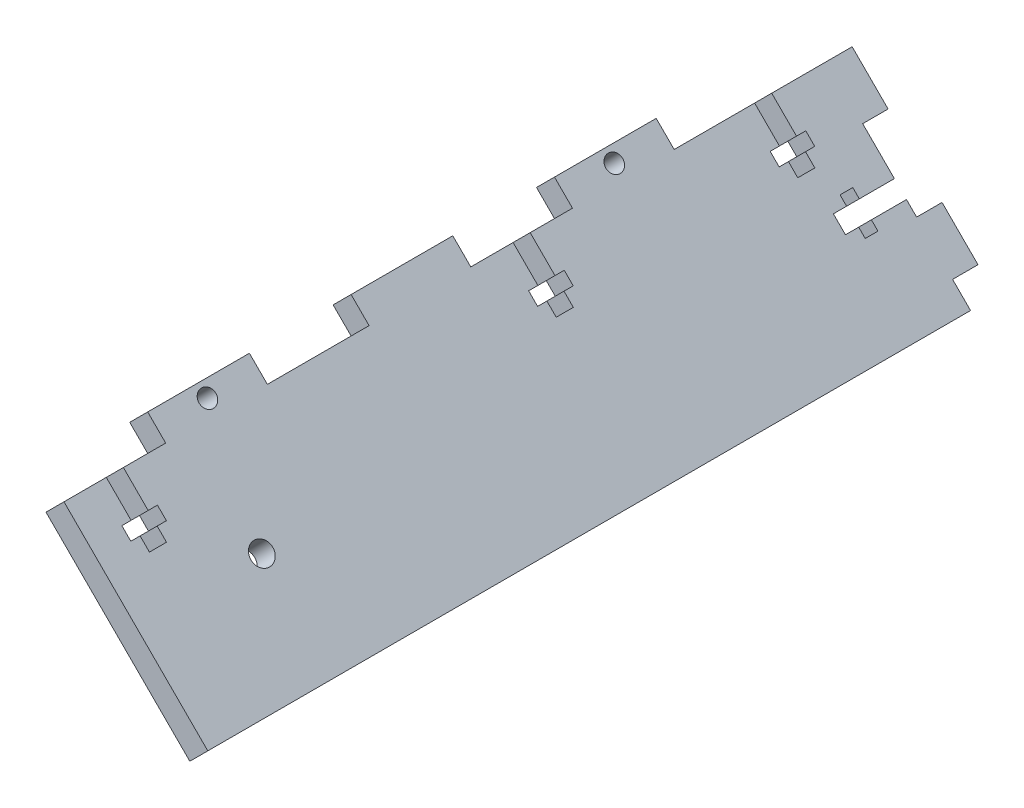
SolidWorks part; units mm, degrees
ref_plane "Front Plane" through (0, 0, 0) normal (0, 0, 1) x (1, 0, 0)
ref_plane "Top Plane" through (0, 0, 0) normal (0, 1, 0) x (1, 0, 0)
ref_plane "Right Plane" through (0, 0, 0) normal (1, 0, 0) x (0, 0, -1)
sketch "Sketch1" plane through (0, 0, 0) normal (0, 0, 1) x (1, 0, 0)
  line L0 (-105.5101, 43.1479) -> (-54.0999, -8.2622) construction
  line L1 (-20.9093, -45.9429) -> (-64.0138, -2.8384) construction
  line L2 (-59.5237, 1.6517) -> (-16.4192, -41.4528) construction
  line L3 (-73.6381, 43.6049) -> (-37.7171, 7.6839)
  line L4 (-73.6381, 43.6049) -> (-69.148, 48.095)
  line L5 (-37.7171, 7.6839) -> (-33.2269, 12.174)
  line L6 (-69.148, 48.095) -> (-33.2269, 12.174)
  line L7 (-70.046, -24.645) -> (-105.967, 11.276) construction
  line L8 (-74.5361, -29.1352) -> (-70.046, -24.645) construction
extrude "Boss-Extrude1" add sketch "Sketch1" along normal up to surface (190.5 mm away)
sketch "Sketch2" plane through (-58.6215, 58.6215, 0) normal (-0.7071, 0.7071, 0) x (0, 0, 1)
  line L0 (190.5, -14.8867) -> (0, -14.8867) construction
  line L1 (165.1, -14.8867) -> (139.7, -14.8867)
  line L2 (165.1, -14.8867) -> (165.1, -21.2367)
  line L3 (165.1, -21.2367) -> (139.7, -21.2367)
  line L4 (139.7, -14.8867) -> (139.7, -21.2367)
  line L5 (190.5, -21.2367) -> (0, -21.2367) construction
  dimension "D1" = 25.4
  dimension "D2" = 25.4
extrude "Boss-Extrude2" add sketch "Sketch2" along normal blind 6.35
pattern_linear "LPattern1" count 3 spacing 50.8 along (0, 0, -1) of "Boss-Extrude2"
sketch "Sketch3" plane through (0, 0, 0) normal (0, 0, -1) x (-1, 0, 0)
  line L0 (73.6381, 43.6049) -> (64.6578, 34.6246)
  line L1 (73.6381, 43.6049) -> (37.7171, 7.6839) construction
  line L2 (64.6578, 34.6246) -> (60.1677, 39.1148)
  line L3 (33.2269, 12.174) -> (69.148, 48.095) construction
  line L4 (60.1677, 39.1148) -> (69.148, 48.095)
  line L5 (69.148, 48.095) -> (73.6381, 43.6049)
  dimension "D1" = 12.7
extrude "Boss-Extrude3" add sketch "Sketch3" along normal blind 6.35
pattern_linear "LPattern2" count 2 spacing 31.75 along (0.7071, -0.7071, 0) of "Boss-Extrude3"
sketch "Sketch4" plane through (-10.5265, -10.5265, 0) normal (0.7071, 0.7071, 0) x (0, 0, -1)
  circle A0 centre (-159.0375, 57.5033) radius 2.7305
extrude "Cut-Extrude1" cut sketch "Sketch4" against normal through all
sketch "Sketch5" plane through (-10.5265, -10.5265, 0) normal (0.7071, 0.7071, 0) x (0, 0, -1)
  line L0 (-177.8, 82.9033) -> (-177.8, 68.4326) construction
  line L1 (-190.5, 82.9033) -> (-165.1, 82.9033) construction
  line L2 (-76.2, 82.9033) -> (-76.2, 62.5112) construction
  line L3 (-88.9, 82.9033) -> (-63.5, 82.9033) construction
  line L4 (-15.875, 82.9033) -> (-15.875, 66.2052) construction
  line L5 (-38.1, 82.9033) -> (6.35, 82.9033) construction
  line L6 (-38.1412, 82.9033) -> (0, 82.9033) construction
  line B0 (-175.6664, 82.9033) -> (-179.9336, 82.9033)
  line B1 (-179.9336, 70.9653) -> (-182.245, 70.9653)
  line B2 (-182.245, 70.9653) -> (-182.245, 74.1403)
  line B3 (-182.245, 74.1403) -> (-179.9336, 74.1403)
  line B4 (-179.9336, 74.1403) -> (-179.9336, 82.9033)
  line B5 (-179.9336, 70.9653) -> (-179.9336, 67.6633)
  line B6 (-179.9336, 67.6633) -> (-175.6664, 67.6633)
  line B7 (-175.6664, 70.9653) -> (-175.6664, 67.6633)
  line B8 (-175.6664, 74.1403) -> (-175.6664, 82.9033)
  line B9 (-173.355, 74.1403) -> (-175.6664, 74.1403)
  line B10 (-173.355, 70.9653) -> (-173.355, 74.1403)
  line B11 (-175.6664, 70.9653) -> (-173.355, 70.9653)
  line B12 (-74.0664, 82.9033) -> (-78.3336, 82.9033)
  line B13 (-78.3336, 70.9653) -> (-80.645, 70.9653)
  line B14 (-80.645, 70.9653) -> (-80.645, 74.1403)
  line B15 (-80.645, 74.1403) -> (-78.3336, 74.1403)
  line B16 (-78.3336, 74.1403) -> (-78.3336, 82.9033)
  line B17 (-78.3336, 70.9653) -> (-78.3336, 67.6633)
  line B18 (-78.3336, 67.6633) -> (-74.0664, 67.6633)
  line B19 (-74.0664, 70.9653) -> (-74.0664, 67.6633)
  line B20 (-74.0664, 74.1403) -> (-74.0664, 82.9033)
  line B21 (-71.755, 74.1403) -> (-74.0664, 74.1403)
  line B22 (-71.755, 70.9653) -> (-71.755, 74.1403)
  line B23 (-74.0664, 70.9653) -> (-71.755, 70.9653)
  line B24 (-13.7414, 82.9033) -> (-18.0086, 82.9033)
  line B25 (-18.0086, 70.9653) -> (-20.32, 70.9653)
  line B26 (-20.32, 70.9653) -> (-20.32, 74.1403)
  line B27 (-20.32, 74.1403) -> (-18.0086, 74.1403)
  line B28 (-18.0086, 74.1403) -> (-18.0086, 82.9033)
  line B29 (-18.0086, 70.9653) -> (-18.0086, 67.6633)
  line B30 (-18.0086, 67.6633) -> (-13.7414, 67.6633)
  line B31 (-13.7414, 70.9653) -> (-13.7414, 67.6633)
  line B32 (-13.7414, 74.1403) -> (-13.7414, 82.9033)
  line B33 (-11.43, 74.1403) -> (-13.7414, 74.1403)
  line B34 (-11.43, 70.9653) -> (-11.43, 74.1403)
  line B35 (-13.7414, 70.9653) -> (-11.43, 70.9653)
sketch_block_instance "TSlot-1"
sketch_block "TSlot" parameters "D1"=3.302, "D2"=3.175
sketch_block_instance "TSlot-2"
sketch_block_instance "TSlot-3"
extrude "Cut-Extrude2" cut sketch "Sketch5" against normal through all
sketch "Sketch6" plane through (-15.0166, -15.0166, 0) normal (-0.7071, -0.7071, 0) x (0, 0, 1)
  line L0 (150.287, 89.2533) -> (154.5542, 82.9033) construction
  line L1 (139.7, 89.2533) -> (165.1, 89.2533) construction
  line L2 (150.287, 89.2533) -> (150.287, 82.9033) construction
  line L3 (154.5542, 89.2533) -> (150.287, 82.9033) construction
  line L4 (154.5542, 82.9033) -> (154.5542, 89.2533) construction
  line L5 (48.687, 89.2533) -> (52.9542, 82.9033) construction
  line L6 (38.1, 89.2533) -> (63.5, 89.2533) construction
  line L7 (48.687, 89.2533) -> (48.687, 82.9033) construction
  line L8 (52.9542, 89.2533) -> (48.687, 82.9033) construction
  line L9 (52.9542, 82.9033) -> (52.9542, 89.2533) construction
  circle A0 centre (152.4206, 86.0783) radius 2.0955
  circle A1 centre (50.8206, 86.0783) radius 2.0955
  dimension "D1" = 4.191
extrude "Cut-Extrude3" cut sketch "Sketch6" against normal through all
sketch "Sketch7" plane through (-10.5265, -10.5265, 0) normal (0.7071, 0.7071, 0) x (0.7071, -0.7071, 0)
  line L0 (-56.8683, 0) -> (-56.8683, -24.4742) construction
  line L1 (-51.1533, 0) -> (-70.2033, 0) construction
  line L4 (-67.6633, -18.0086) -> (-67.6633, -13.7414) construction
  line B0 (-54.7347, 0) -> (-59.0019, 0)
  line B1 (-59.0019, -11.938) -> (-61.3133, -11.938)
  line B2 (-61.3133, -11.938) -> (-61.3133, -8.763)
  line B3 (-61.3133, -8.763) -> (-59.0019, -8.763)
  line B4 (-59.0019, -8.763) -> (-59.0019, 0)
  line B5 (-59.0019, -11.938) -> (-59.0019, -15.24)
  line B6 (-59.0019, -15.24) -> (-54.7347, -15.24)
  line B7 (-54.7347, -11.938) -> (-54.7347, -15.24)
  line B8 (-54.7347, -8.763) -> (-54.7347, 0)
  line B9 (-52.4233, -8.763) -> (-54.7347, -8.763)
  line B10 (-52.4233, -11.938) -> (-52.4233, -8.763)
  line B11 (-54.7347, -11.938) -> (-52.4233, -11.938)
  dimension "D1" = 6.35
sketch_block_instance "TSlot-4"
extrude "Cut-Extrude4" cut sketch "Sketch7" against normal through all
